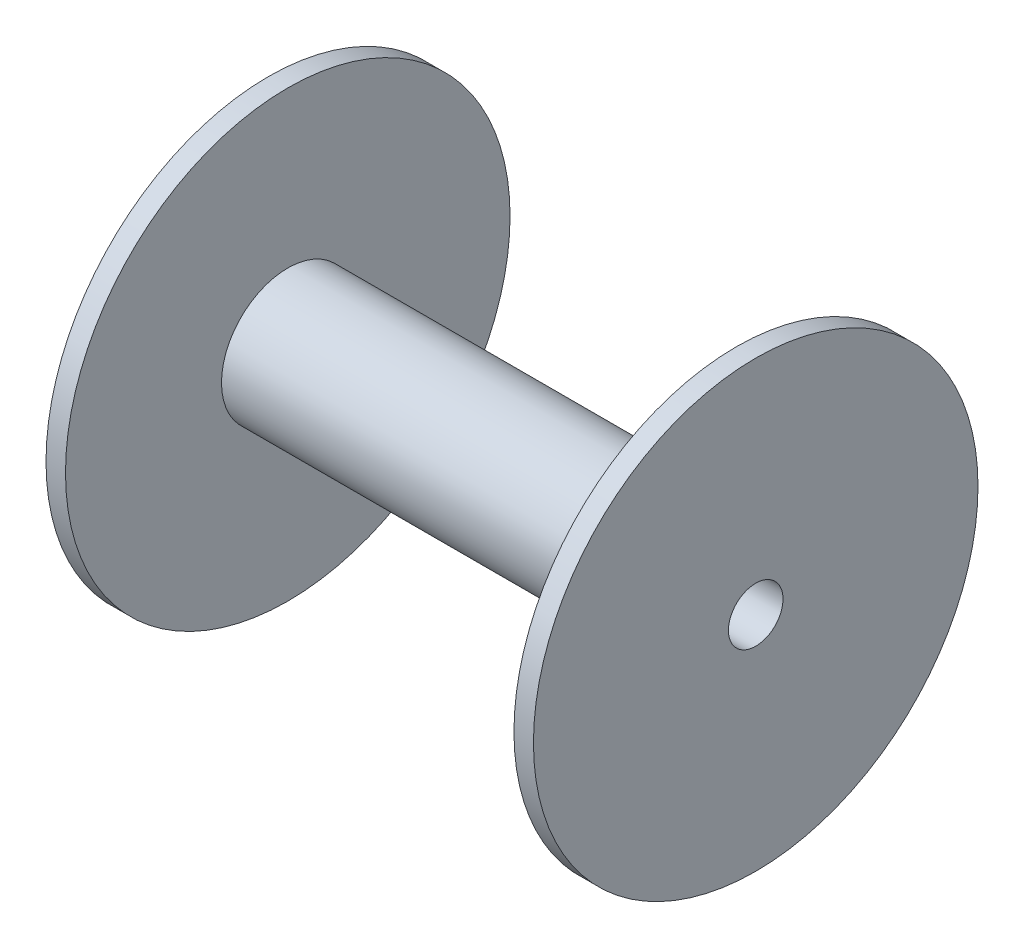
SolidWorks part; units mm, degrees
ref_plane "Front Plane" through (0, 0, 0) normal (0, 0, 1) x (1, 0, 0)
ref_plane "Top Plane" through (0, 0, 0) normal (0, 1, 0) x (1, 0, 0)
ref_plane "Right Plane" through (0, 0, 0) normal (1, 0, 0) x (0, 0, -1)
sketch "Sketch1" plane through (0, 0, 0) normal (0, 0, 1) x (1, 0, 0)
  line L0 (-75, 0) -> (75, 0) construction
  line L2 (-62.5, 57) -> (-57.5, 57)
  line L3 (-57.5, 57) -> (-57.5, 17)
  line L4 (-57.5, 17) -> (57.5, 17)
  line L12 (-62.5, 57) -> (-62.5, 7)
  line L13 (-62.5, 7) -> (62.5, 7)
  line L15 (0, 0) -> (0, 14) construction
  line L16 (62.5, 7) -> (62.5, 57)
  line L17 (62.5, 57) -> (57.5, 57)
  line L18 (57.5, 57) -> (57.5, 17)
  line L19 (75, 0) -> (75, 67.6816) construction
  line L20 (62.5, 7) -> (75, 7) construction
  point P4 (0, 0)
  point P14 (0, 7)
  point P15 (75, 7)
  dimension "D1" = 150
  dimension "D2" = 5
  dimension "D3" = 40
  dimension "D4" = 7
  dimension "D5" = 40
  dimension "D6" = 50
  dimension "D7" = 12.5
  dimension "D8" = 67.6816
  dimension "D9" = 5
revolve "Revolve1" add sketch "Sketch1" angle 360 about L0
